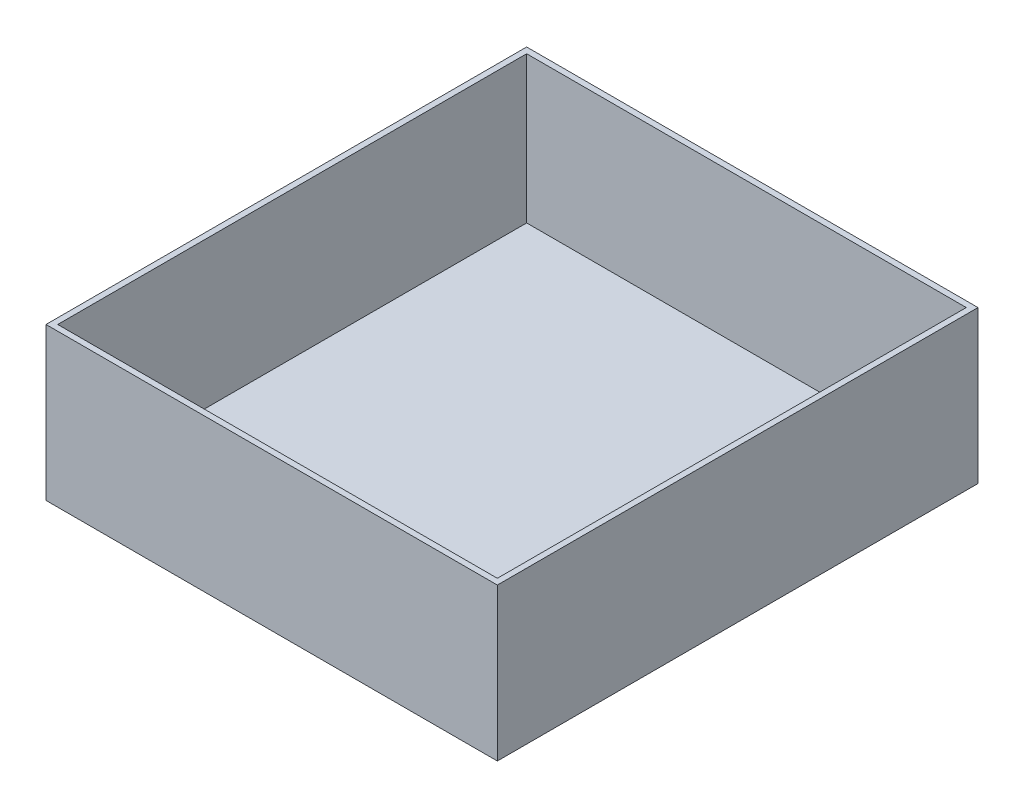
SolidWorks part; units mm, degrees
material "ABS"
ref_plane "Front Plane" through (0, 0, 0) normal (0, 0, 1) x (1, 0, 0)
ref_plane "Top Plane" through (0, 0, 0) normal (0, 1, 0) x (1, 0, 0)
ref_plane "Right Plane" through (0, 0, 0) normal (1, 0, 0) x (0, 0, -1)
sketch "Sketch2" plane through (0, 0, 0) normal (0, 1, 0) x (1, 0, 0)
  line L0 (-77, 82) -> (-77, -82)
  line L1 (-75, 80) -> (75, 80)
  line L2 (-75, 80) -> (-75, -80)
  line L3 (-75, -80) -> (75, -80)
  line L4 (75, 80) -> (75, -80)
  line L5 (-75, 80) -> (75, -80) construction
  line L6 (-75, -80) -> (75, 80) construction
  line L7 (-77, -82) -> (77, -82)
  line L8 (77, 82) -> (77, -82)
  line L9 (-77, 82) -> (77, 82)
  point P0 (0, 0)
  dimension "D1" = 160
  dimension "D2" = 150
  dimension "D3" = 2
extrude "Walls" add sketch "Sketch2" along normal blind 50
sketch "Sketch3" plane through (0, 0, 0) normal (0, -1, 0) x (1, 0, 0)
  line L1 (-77, -82) -> (77, -82)
  line L2 (-77, -82) -> (-77, 82)
  line L3 (-77, 82) -> (77, 82)
  line L4 (77, -82) -> (77, 82)
  line L5 (-77, -82) -> (77, 82) construction
  line L6 (-77, 82) -> (77, -82) construction
  point P0 (0, 0)
extrude "Base" add sketch "Sketch3" along normal blind 2
